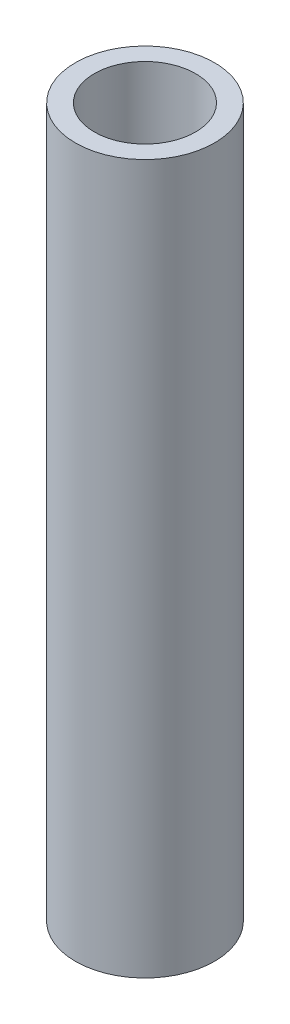
SolidWorks part; units mm, degrees
ref_plane "Front Plane" through (0, 0, 0) normal (0, 0, 1) x (1, 0, 0)
ref_plane "Top Plane" through (0, 0, 0) normal (0, 1, 0) x (1, 0, 0)
ref_plane "Right Plane" through (0, 0, 0) normal (1, 0, 0) x (0, 0, -1)
sketch "Sketch1" plane through (0, 0, 0) normal (0, 1, 0) x (1, 0, 0)
  circle A0 centre (0, 0) radius 12.1539
  circle A1 centre (0, 0) radius 16.7005
  dimension "D1" = 24.3078
  dimension "D2" = 33.401
extrude "Boss-Extrude1" add sketch "Sketch1" along normal mid plane 170.18
